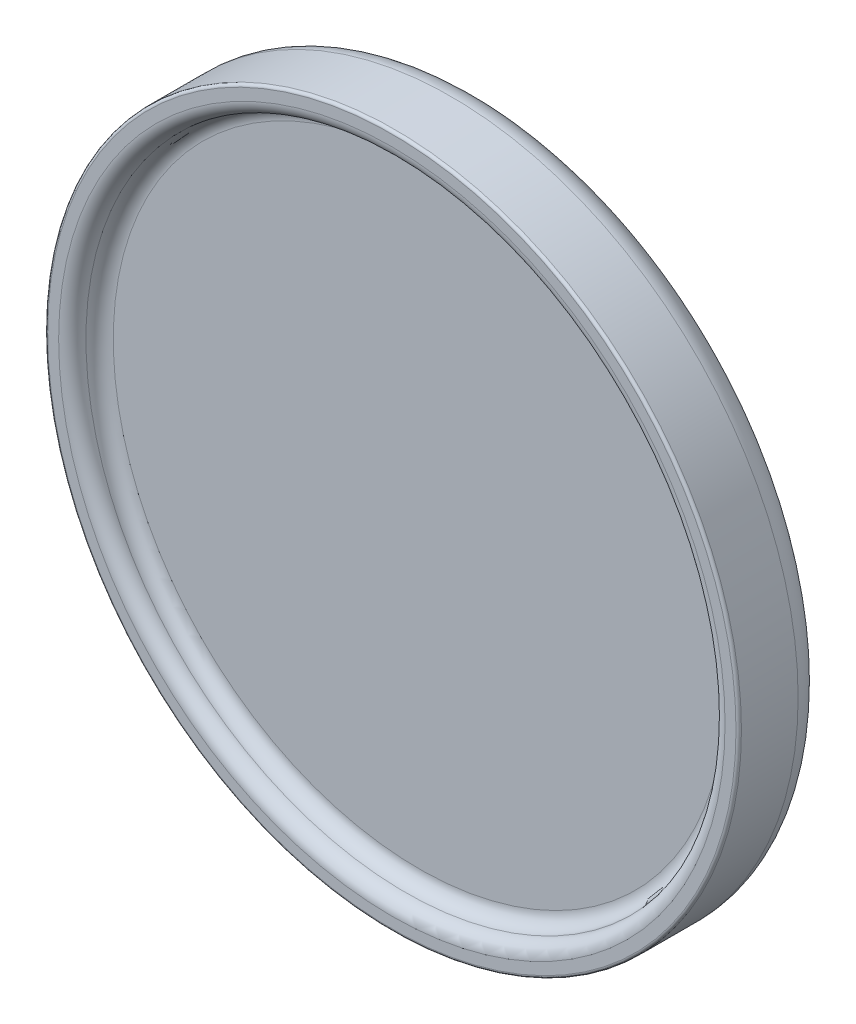
SolidWorks part; units mm, degrees
extrude "Base-Extrude" add sketch "Sketch1" against normal blind 31.75
sketch "Sketch1" plane through (0, 0, 0) normal (0, 0, 1) x (1, 0, 0)
  circle A0 centre (0, 0) radius 127
  dimension "D1" = 254
material "PW100:Mi:0:241:Ar:0:-1:Re:24:"
ref_plane "Front" through (0, 0, 0) normal (0, 0, 1) x (1, 0, 0)
ref_plane "Top" through (0, 0, 0) normal (0, 1, 0) x (1, 0, 0)
ref_plane "Right" through (0, 0, 0) normal (1, 0, 0) x (0, 0, -1)
other "Configuration Table"
sketch "Sketch3" plane through (0, 0, 0) normal (0, 0, 1) x (1, 0, 0)
  circle A2 centre (0, 0) radius 117
  circle A3 centre (0, 0) radius 117
  dimension "D1" = 10
extrude "Cut-Extrude1" cut sketch "Sketch3" against normal blind 10
fillet "Fillet1" radius 5 1 edges at (117, 0, 0)
fillet "Fillet2" radius 5 1 edges at (117, 0, -10)
fillet "Fillet3" radius 1 1 edges at (127, 0, 0)
fillet "Fillet4" radius 10 1 edges at (127, 0, -31.75)
scale "Scale2" scale about centroid uniform scaling yes scale factor 1.2
